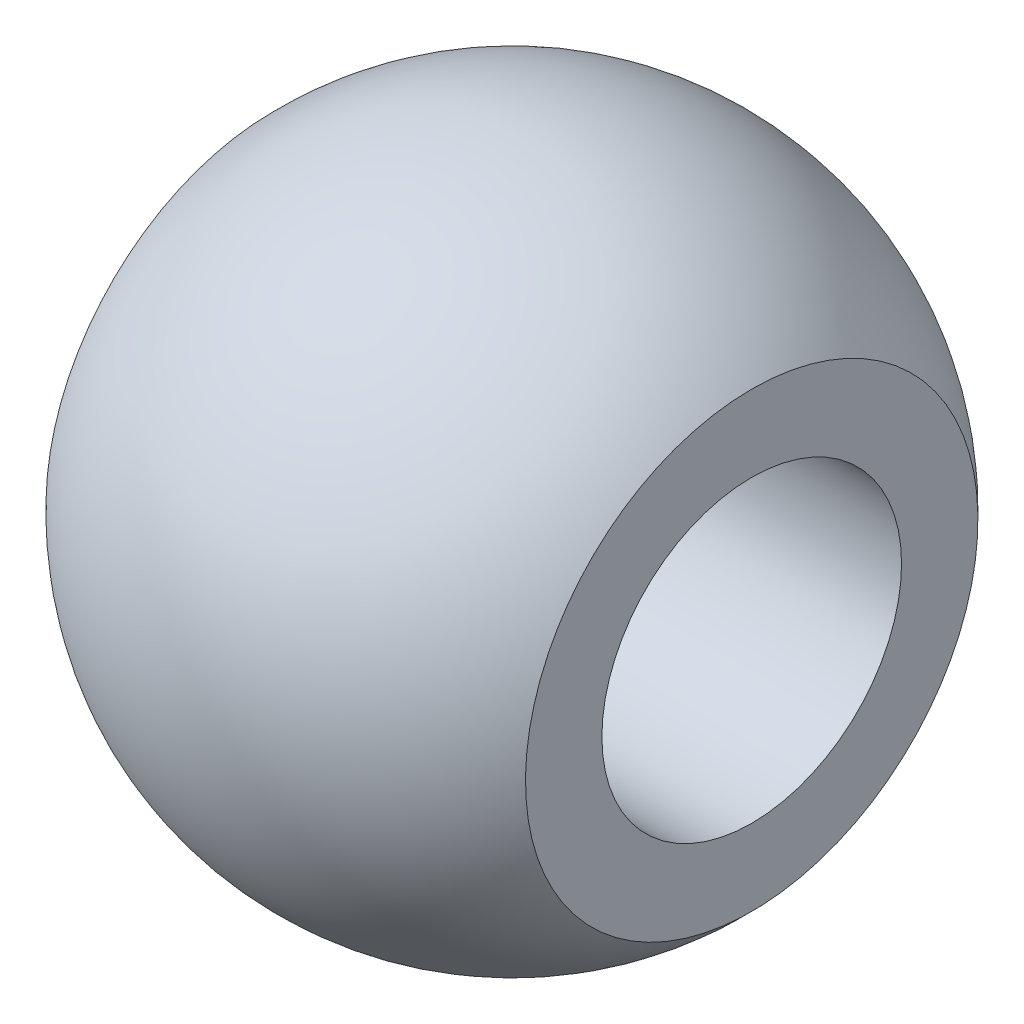
SolidWorks part; units mm, degrees
ref_plane "Front Plane" through (0, 0, 0) normal (0, 0, 1) x (1, 0, 0)
ref_plane "Top Plane" through (0, 0, 0) normal (0, 1, 0) x (1, 0, 0)
ref_plane "Right Plane" through (0, 0, 0) normal (1, 0, 0) x (0, 0, -1)
sketch "Sketch1" plane through (0, 0, 0) normal (0, 0, 1) x (1, 0, 0)
  line L0 (-6.0771, 0) -> (6.6622, 0) construction
  line L1 (0, 9.2819) -> (0, -7.234) construction
  line L2 (-4, 3.7749) -> (-4, 2.5)
  line L3 (-4, 2.5) -> (4, 2.5)
  line L4 (4, 3.7749) -> (4, 2.5)
  arc A0 (-4, 3.7749) -> (4, 3.7749) centre (0, 0) cw
  point P10 (0, 2.5)
  dimension "D2" = 5.5
  dimension "D1" = 5
  dimension "D3" = 4
revolve "Revolve1" add sketch "Sketch1" angle 360 about L0
ref_point "Point1"
ref_axis "Axis1" through (-6.7141, 0, 0) along (1, 0, 0)
